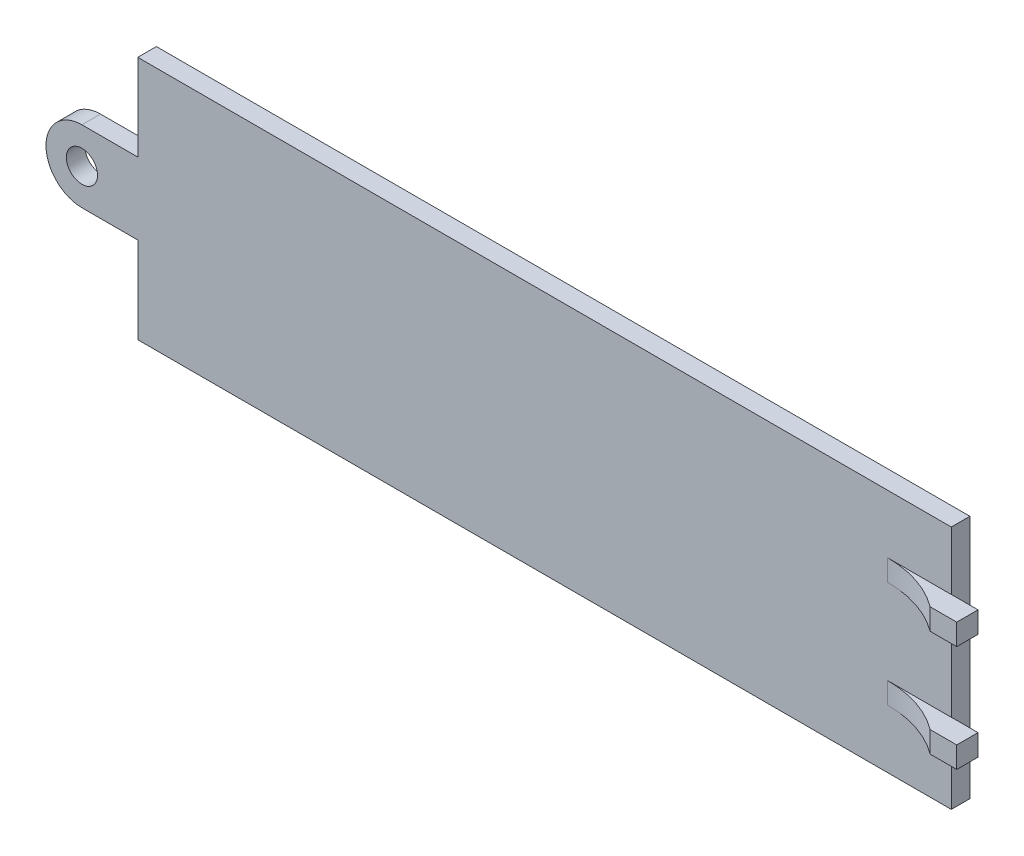
SolidWorks part; units mm, degrees
ref_plane "Plano frontal" through (0, 0, 0) normal (1, 0, 0) x (0, 1, 0)
ref_plane "Plano superior" through (0, 0, 0) normal (0, 0, 1) x (0, 1, 0)
ref_plane "Plano direito" through (0, 0, 0) normal (0, 1, 0) x (-1, 0, 0)
sketch "Esboço1" plane through (0, 0, 0) normal (0, 0, 1) x (0, 1, 0)
  line L0 (3.3786, 38.25) -> (11.5, 38.25)
  line L1 (-11.5, 38.25) -> (-3.3786, 38.25)
  line L2 (-11.5, 38.25) -> (-11.5, -38.25)
  line L3 (-11.5, -38.25) -> (11.5, -38.25)
  line L4 (11.5, 38.25) -> (11.5, -38.25)
  line L5 (-11.5, 38.25) -> (11.5, -38.25) construction
  line L6 (-11.5, -38.25) -> (11.5, 38.25) construction
  line L7 (-3.3786, 43.5) -> (3.3786, 43.5) construction
  line L8 (-3.3786, 43.5) -> (-3.3786, 38.25)
  line L10 (3.3786, 43.5) -> (3.3786, 38.25)
  line L11 (-3.3786, 43.5) -> (3.3786, 38.25) construction
  line L12 (-3.3786, 38.25) -> (3.3786, 43.5) construction
  arc A0 (-3.3786, 43.5) -> (3.3786, 43.5) centre (0, 43.5) cw
  circle A1 centre (0, 43.5) radius 1.4658
  point P0 (0, 0)
  point P6 (0, 40.875)
  dimension "D1" = 5.25
  dimension "77" = 76.5
  dimension "17,5" = 23
  dimension "D2" = 6.7571
extrude "Ressalto-extrusão1" add sketch "Esboço1" along normal blind 1.75
sketch "Esboço2" plane through (38.25, 0, 0) normal (1, 0, 0) x (0, 0, -1)
  line L0 (-1.75, -11.5) -> (-1.75, 11.5) construction
  line L5 (-2.74, 5) -> (-2.74, -5) construction
  line L6 (-3.74, -6) -> (-1.74, -6)
  line L7 (-3.74, -6) -> (-3.74, -4)
  line L12 (-3.74, -4) -> (-1.74, -4)
  line L13 (-1.74, -6) -> (-1.74, -4)
  line L14 (-3.74, -6) -> (-1.74, -4) construction
  line L15 (-3.74, -4) -> (-1.74, -6) construction
  line L16 (-3.74, 4) -> (-1.74, 4)
  line L17 (-3.74, 4) -> (-3.74, 6)
  line L18 (-3.74, 6) -> (-1.74, 6)
  line L19 (-1.74, 4) -> (-1.74, 6)
  line L20 (-3.74, 4) -> (-1.74, 6) construction
  line L21 (-3.74, 6) -> (-1.74, 4) construction
  point P0 (-2.74, -5)
  point P7 (-2.74, 5)
  point P14 (-2.74, 0)
  dimension "D1" = 10
  dimension "D2" = 2
  dimension "D3" = 0.99
extrude "Ressalto-extrusão2" add sketch "Esboço2" along normal blind 2.5
fillet "Filete1" radius 10 2 edges at (38.25, -5, 1.75) (38.25, 5, 1.75)
sketch "Esboço3" plane through (40.75, 0, 0) normal (1, 0, 0) x (0, 1, 0)
  line L0 (-6, 3.74) -> (-4, 1.74) construction
